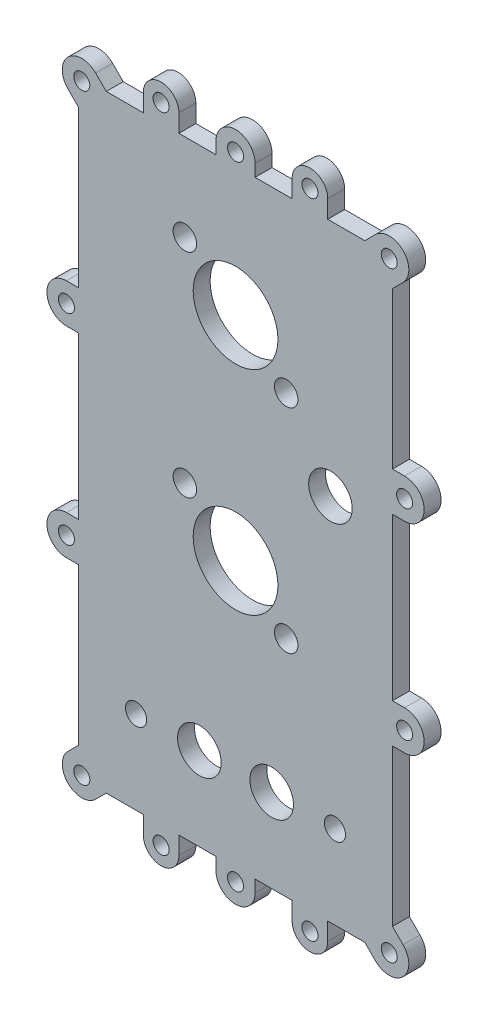
SolidWorks part; units mm, degrees
material "Acrylic (Medium-high impact)"
ref_plane "X-Y Datum" through (0, 0, 0) normal (0, 0, 1) x (1, 0, 0)
ref_plane "X-Z Datum" through (0, 0, 0) normal (0, 1, 0) x (1, 0, 0)
ref_plane "Y-Z Datum" through (0, 0, 0) normal (1, 0, 0) x (0, 0, -1)
sketch "Sketch1" plane through (0, 0, 0) normal (0, 0, 1) x (1, 0, 0)
  line L60 (50.35, 7.779) -> (19.5282, 7.779)
  line L61 (50.35, 11.1887) -> (50.35, 7.779)
  line L62 (61.35, 7.779) -> (61.35, 11.1887)
  line L63 (92.1718, 7.779) -> (61.35, 7.779)
  line L64 (95.1523, 10.7595) -> (92.1718, 7.779)
  line L65 (99.95, 0.0008) -> (102.9304, 2.9813)
  line L66 (99.95, -43.902) -> (99.95, 0.0008)
  line L67 (103.3597, -43.902) -> (99.95, -43.902)
  line L68 (99.95, -54.902) -> (103.3597, -54.902)
  line L69 (99.95, -100.29) -> (99.95, -54.902)
  line L70 (103.3597, -100.29) -> (99.95, -100.29)
  line L71 (99.95, -111.29) -> (103.3597, -111.29)
  line L72 (99.95, -155.1928) -> (99.95, -111.29)
  line L73 (102.9304, -158.1733) -> (99.95, -155.1928)
  line L74 (92.1718, -162.971) -> (95.1523, -165.9514)
  line L75 (61.35, -162.971) -> (92.1718, -162.971)
  line L76 (61.35, -166.3807) -> (61.35, -162.971)
  line L77 (50.35, -162.971) -> (50.35, -166.3807)
  line L78 (19.5282, -162.971) -> (50.35, -162.971)
  line L79 (16.5477, -165.9514) -> (19.5282, -162.971)
  line L80 (11.75, -155.1928) -> (8.7695, -158.1733)
  line L81 (11.75, -111.29) -> (11.75, -155.1928)
  line L82 (8.3403, -111.29) -> (11.75, -111.29)
  line L83 (11.75, -100.29) -> (8.3403, -100.29)
  line L84 (11.75, -54.902) -> (11.75, -100.29)
  line L85 (8.3403, -54.902) -> (11.75, -54.902)
  line L86 (11.75, -43.902) -> (8.3403, -43.902)
  line L87 (11.75, 0.0008) -> (11.75, -43.902)
  line L88 (8.7695, 2.9813) -> (11.75, 0.0008)
  line L89 (19.5282, 7.779) -> (16.5477, 10.7595)
  arc A20 (61.35, 11.1887) -> (50.35, 11.1887) centre (55.85, 11.1887) ccw
  arc A21 (102.9304, 2.9813) -> (95.1523, 10.7595) centre (99.0413, 6.8704) ccw
  arc A22 (103.3597, -54.902) -> (103.3597, -43.902) centre (103.3597, -49.402) ccw
  arc A23 (103.3597, -111.29) -> (103.3597, -100.29) centre (103.3597, -105.79) ccw
  arc A24 (95.1523, -165.9514) -> (102.9304, -158.1733) centre (99.0413, -162.0624) ccw
  arc A25 (50.35, -166.3807) -> (61.35, -166.3807) centre (55.85, -166.3807) ccw
  arc A26 (8.7695, -158.1733) -> (16.5477, -165.9514) centre (12.6586, -162.0624) ccw
  arc A27 (8.3403, -100.29) -> (8.3403, -111.29) centre (8.3403, -105.79) ccw
  arc A28 (8.3403, -43.902) -> (8.3403, -54.902) centre (8.3403, -49.402) ccw
  arc A29 (16.5477, 10.7595) -> (8.7695, 2.9813) centre (12.6586, 6.8704) ccw
extrude "Boss-Extrude1" add sketch "Sketch1" against normal blind 4.7625
hole_wizard "M4 Clearance Hole1" positions "Sketch2" profile "Sketch3" hole size "M4" standard "ANSI Metric" end condition through all
sketch "Sketch2" plane through (0, 0, -4.7625) normal (0, 0, -1) x (-1, 0, 0)
  point P0 (-12.6586, -162.0624)
  point P2 (-55.85, -166.3807)
  point P4 (-99.0413, -162.0624)
  point P6 (-103.3597, -105.79)
  point P8 (-103.3597, -49.402)
  point P10 (-99.0413, 6.8704)
  point P14 (-12.6586, 6.8704)
  point P16 (-8.3403, -49.402)
  point P18 (-8.3403, -105.79)
  point P22 (-55.85, 11.1887)
sketch "Sketch3" plane through (12.6586, -162.0624, -4.7625) normal (1, 0, 0) x (0, 1, 0)
  line L0 (0, 0) -> (0, 4.7625)
  line L1 (0, 4.7625) -> (2.25, 4.7625)
  line L2 (2.25, 4.7625) -> (2.25, 0)
  line L5 (2.25, 0) -> (0, 0)
  line L11 (0, -6.35) -> (0, 107.95) construction
  dimension "Thru Hole Dia." = 4.5
  dimension "Thru Hole Depth" = 4.7625
sketch "Sketch4" plane through (0, 0, -4.7625) normal (0, 0, -1) x (-1, 0, 0)
  line L8 (-93.95, -3.555) -> (-93.95, -119.546)
  line L9 (-93.95, -119.546) -> (-17.75, -119.546)
  line L10 (-17.75, -119.546) -> (-17.75, -3.555)
  line L11 (-23.084, 1.779) -> (-88.616, 1.779)
  line L16 (-95.5403, -3.555) -> (-95.5403, -151.637)
  line L17 (-88.616, -158.5613) -> (-23.084, -158.5613)
  line L18 (-16.1597, -151.637) -> (-16.1597, -3.555)
  line L19 (-23.084, 3.3693) -> (-88.616, 3.3693)
  line L24 (-93.95, -122.046) -> (-93.95, -151.637)
  line L25 (-17.75, -122.046) -> (-93.95, -122.046)
  line L26 (-17.75, -151.637) -> (-17.75, -122.046)
  line L27 (-88.616, -156.971) -> (-23.084, -156.971)
  circle A0 centre (-41.6161, -16.6659) radius 3.3
  circle A1 centre (-70.0839, -40.3003) radius 3.3
  circle A2 centre (-27.91, -139.5085) radius 2.9766
  circle A3 centre (-41.6161, -76.4667) radius 3.3
  circle A4 centre (-83.79, -139.5085) radius 2.9766
  circle A5 centre (-70.0839, -100.1011) radius 3.3
  arc A8 (-17.75, -3.555) -> (-23.084, 1.779) centre (-23.084, -3.555) ccw
  arc A9 (-88.616, 1.779) -> (-93.95, -3.555) centre (-88.616, -3.555) ccw
  circle A14 centre (-66.01, -139.5085) radius 6.125
  arc A16 (-95.5403, -151.637) -> (-88.616, -158.5613) centre (-88.616, -151.637) ccw
  arc A17 (-23.084, -158.5613) -> (-16.1597, -151.637) centre (-23.084, -151.637) ccw
  arc A18 (-16.1597, -3.555) -> (-23.084, 3.3693) centre (-23.084, -3.555) ccw
  arc A19 (-88.616, 3.3693) -> (-95.5403, -3.555) centre (-88.616, -3.555) ccw
  arc A22 (-23.084, -156.971) -> (-17.75, -151.637) centre (-23.084, -151.637) ccw
  arc A23 (-93.95, -151.637) -> (-88.616, -156.971) centre (-88.616, -151.637) ccw
  circle A32 centre (-82.52, -59.221) radius 6.125
  circle A34 centre (-45.69, -139.5085) radius 6.125
  circle A36 centre (-55.85, -88.2839) radius 11.9
  circle A38 centre (-55.85, -28.4831) radius 11.9
  dimension "D1" = 6.6
  dimension "D2" = 12.25
  dimension "D3" = 5.9531
  dimension "D4" = 23.8
  dimension "D5" = 12.25
  dimension "D7" = 12.25
  dimension "D6" = 55.88
extrude "Cut-Extrude1" cut sketch "Sketch4" against normal blind 4.7625 contours A38 | A32 | A36 | A2 | A34 | A14 | A4 | A0 | A1 | A3 | A5 region at (41.6161, -16.6659, -4.7625) region at (70.0839, -40.3003, -4.7625) region at (27.91, -139.5085, -4.7625) region at (41.6161, -76.4667, -4.7625) region at (83.79, -139.5085, -4.7625) region at (70.0839, -100.1011, -4.7625) region at (66.01, -139.5085, -4.7625) region at (82.52, -59.221, -4.7625) region at (45.69, -139.5085, -4.7625) region at (55.85, -88.2839, -4.7625) region at (55.85, -28.4831, -4.7625)
sketch "Sketch5" plane through (0, 0, -6.35) normal (0, 0, -1) x (-1, 0, 0)
  line L0 (-99.95, -77.596) -> (-104.95, -77.596) construction
  line L1 (-99.95, -100.29) -> (-99.95, -54.902) construction
  line L2 (-34.9391, 7.779) -> (-34.9391, 12.779) construction
  line L3 (-50.35, 7.779) -> (-19.5282, 7.779) construction
  line L4 (-76.7609, -162.971) -> (-76.7609, -167.971) construction
  line L5 (-29.9391, 12.779) -> (-29.9391, 7.779)
  line L6 (-61.35, -162.971) -> (-92.1718, -162.971) construction
  line L7 (-104.95, -72.596) -> (-99.95, -72.596)
  line L8 (-104.95, -82.596) -> (-99.95, -82.596)
  line L9 (-81.7609, -167.971) -> (-81.7609, -162.971)
  line L10 (-71.7609, -167.971) -> (-71.7609, -162.971)
  line L11 (-29.9391, 12.779) -> (-29.9391, 7.779)
  line L12 (-39.9391, 12.779) -> (-39.9391, 7.779)
  line L13 (-81.7609, -162.971) -> (-71.7609, -162.971)
  line L14 (-99.95, -82.596) -> (-99.95, -72.596)
  line L15 (-39.9391, 7.779) -> (-29.9391, 7.779)
  line L16 (-28.3269, -167.971) -> (-28.3269, -162.3607)
  line L17 (-55.0439, -178.7796) -> (-55.0439, -155.8273) construction
  line L19 (-28.3269, -162.3607) -> (-38.3269, -162.3607)
  line L20 (-38.3269, -167.971) -> (-38.3269, -162.3607)
  line L21 (-39.9391, 12.779) -> (-39.9391, 7.779)
  line L22 (-29.9391, 12.779) -> (-29.9391, 7.779)
  line L23 (-29.9391, 12.779) -> (-29.9391, 7.779)
  line L24 (-39.9391, 12.779) -> (-39.9391, 7.779)
  line L25 (-39.9391, 12.779) -> (-39.9391, 7.779)
  line L26 (-29.9391, 12.779) -> (-29.9391, 7.779)
  line L27 (-39.9391, 12.779) -> (-39.9391, 7.779)
  line L29 (-70.0711, 12.779) -> (-70.0711, 7.3696)
  line L30 (-70.0711, 7.3696) -> (-80.0711, 7.3696)
  line L31 (-80.0711, 12.779) -> (-80.0711, 7.3696)
  circle A1 centre (-103.3597, -105.79) radius 2.25
  circle A2 centre (-104.95, -77.596) radius 2.25 construction
  circle A3 centre (-34.9391, 12.779) radius 2.25 construction
  circle A4 centre (-76.7609, -167.971) radius 2.25 construction
  circle A5 centre (-104.95, -77.596) radius 4 construction
  circle A6 centre (-104.95, -77.596) radius 5
  circle A7 centre (-76.7609, -167.971) radius 5
  circle A8 centre (-34.9391, 12.779) radius 5
  arc A11 (-80.0711, 12.779) -> (-70.0711, 12.779) centre (-75.0711, 12.779) cw
  arc A12 (-28.3269, -167.971) -> (-38.3269, -167.971) centre (-33.3269, -167.971) cw
  circle A14 centre (-75.0711, 12.779) radius 2.25
  circle A15 centre (-33.3269, -167.971) radius 2.25
  dimension "D1" = 4.5
  dimension "D2" = 4.5
  dimension "D4" = 8
  dimension "D5" = 10
  dimension "D3" = 5
sketch "Sketch6" plane through (0, 0, 0) normal (0, 0, 1) x (1, 0, 0)
  line L0 (39.9391, 12.779) -> (39.9391, 7.779) construction
  line L1 (39.9391, 7.779) -> (29.9391, 7.779) construction
  line L2 (29.9391, 12.779) -> (29.9391, 7.779) construction
  line L3 (81.7609, -167.971) -> (81.7609, -162.971) construction
  line L4 (81.7609, -162.971) -> (71.7609, -162.971) construction
  line L5 (71.7609, -167.971) -> (71.7609, -162.971) construction
  line L9 (39.9391, 12.779) -> (39.9391, 7.779)
  line L10 (39.9391, 7.779) -> (29.9391, 7.779)
  line L11 (29.9391, 12.779) -> (29.9391, 7.779)
  line L12 (81.7609, -167.971) -> (81.7609, -162.971)
  line L13 (81.7609, -162.971) -> (71.7609, -162.971)
  line L14 (71.7609, -167.971) -> (71.7609, -162.971)
  circle A1 centre (103.3597, -105.79) radius 2.25
  circle A2 centre (103.3597, -105.79) radius 2.25
  circle A3 centre (34.9391, 12.779) radius 5
  circle A4 centre (34.9391, 12.779) radius 5
  circle A5 centre (76.7609, -167.971) radius 5
  circle A6 centre (76.7609, -167.971) radius 5
  dimension "D1" = 0
  dimension "D2" = 0
  dimension "D3" = 0
extrude "Boss-Extrude3" add sketch "Sketch6" against normal blind 4.7625 contours A6 L12 L13 L14 | A4 L11 L10 L9 | A4 | A4 L10 L9 | A6 L13 L14 | A6 region at (34.9391, 12.779, 0) region at (38.8222, 8.8959, 0) region at (31.0559, 8.8959, 0) region at (80.644, -164.0878, 0) region at (72.8777, -164.0878, 0)
hole_wizard "M4 Clearance Hole2" positions "Sketch8" profile "Sketch9" hole size "M4" standard "ANSI Metric" end condition through all
sketch "Sketch8" plane through (0, 0, 0) normal (0, 0, 1) x (1, 0, 0)
  point P11 (34.9391, 12.779)
  point P15 (76.7609, -167.971)
sketch "Sketch9" plane through (34.9391, 12.779, 0) normal (1, 0, 0) x (0, -1, 0)
  line L0 (0, 0) -> (0, 4.7625)
  line L1 (0, 4.7625) -> (2.25, 4.7625)
  line L2 (2.25, 4.7625) -> (2.25, 0)
  line L5 (2.25, 0) -> (0, 0)
  line L11 (0, -6.35) -> (0, 107.95) construction
  dimension "Thru Hole Dia." = 4.5
  dimension "Thru Hole Depth" = 4.7625
ref_plane "Plane1" through (55.85, 0, 0) normal (-1, 0, 0) x (0, 0, 1)
mirror "Mirror1" about plane through (55.85, 0, 0) normal (-1, 0, 0) of "M4 Clearance Hole2", "Boss-Extrude3"
